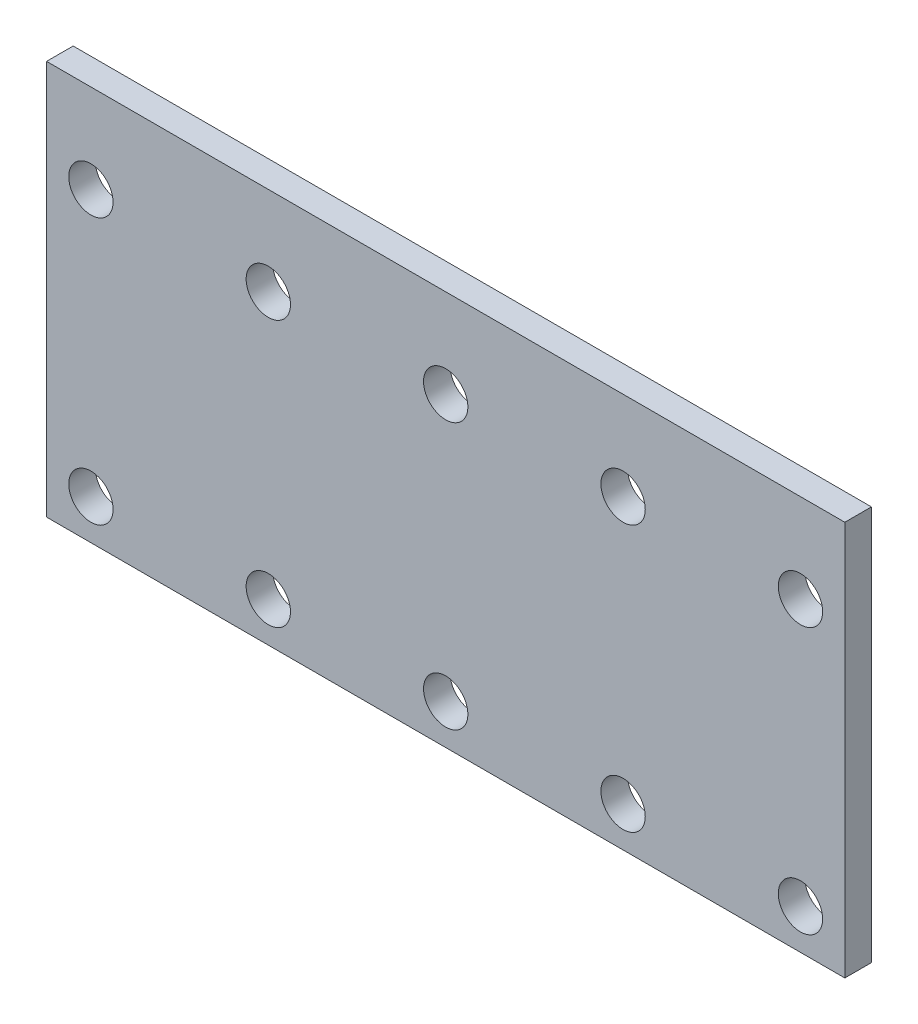
SolidWorks part; units mm, degrees
material "ABS"
ref_plane "Front Plane" through (0, 0, 0) normal (0, 0, 1) x (1, 0, 0)
ref_plane "Top Plane" through (0, 0, 0) normal (0, 1, 0) x (1, 0, 0)
ref_plane "Right Plane" through (0, 0, 0) normal (1, 0, 0) x (0, 0, -1)
sketch "Sketch1" plane through (0, 0, 0) normal (0, 0, 1) x (1, 0, 0)
  line L0 (0, 14.5) -> (0, 44.5)
  line L1 (0, 0) -> (90, 0)
  line L2 (0, 0) -> (0, 14.5)
  line L3 (0, 14.5) -> (90, 14.5)
  line L4 (90, 0) -> (90, 14.5)
  line L5 (0, 44.5) -> (90, 44.5)
  line L6 (90, 44.5) -> (90, 14.5)
  line L7 (0, 4.5) -> (90, 4.5) construction
  line L8 (0, 34.5) -> (90, 34.5) construction
  line L9 (5, 34.5) -> (5, 4.5) construction
  circle A0 centre (5, 34.5) radius 2.5
  circle A1 centre (5, 4.5) radius 2.5
  circle A2 centre (25, 4.5) radius 2.5
  circle A3 centre (25, 34.5) radius 2.5
  circle A4 centre (45, 4.5) radius 2.5
  circle A5 centre (45, 34.5) radius 2.5
  circle A6 centre (65, 4.5) radius 2.5
  circle A7 centre (65, 34.5) radius 2.5
  circle A8 centre (85, 4.5) radius 2.5
  circle A9 centre (85, 34.5) radius 2.5
  point P4 (5, 37)
  point P16 (5, 2)
  dimension "D4" = 5
  dimension "D5" = 5
  dimension "D1" = 10
  dimension "D2" = 20
  dimension "D3" = 90
  dimension "D6" = 5
  dimension "D8" = 2
  dimension "D9" = 10
  dimension "D7" = 5
extrude "Boss-Extrude1" add sketch "Sketch1" along normal blind 3 contours L1 L4 L3 L2 A4 A2 A1 | L6 L5 L0 L3 A5 A3 A0 region at (45, 7.4737, 0) region at (45, 29.3113, 0)
sketch "Sketch2" [suppressed] plane through (0, 0, 0) normal (0, 0, 1) x (1, 0, 0)
  line L0 (0, 20) -> (20, 20) construction
  line L1 (0, 0) -> (40, 0)
  line L2 (0, 0) -> (0, 30)
  line L3 (0, 30) -> (40, 30)
  line L4 (40, 0) -> (40, 30)
  line L5 (20, 20) -> (40, 20) construction
  circle A0 centre (10, 20) radius 2.5
  circle A1 centre (30, 20) radius 2.5
  circle A2 centre (20, 20) radius 2.5
  point P7 (10, 20)
  point P9 (30, 20)
  dimension "D1" = 5
  dimension "D2" = 30
  dimension "D3" = 20
  dimension "D4" = 40
extrude "Boss-Extrude2" [suppressed] add sketch "Sketch2" along normal blind 3
sketch "Sketch3" [suppressed] plane through (0, 0, 0) normal (0, 1, 0) x (1, 0, 0)
  line L0 (0, -10) -> (20, -10) construction
  line L1 (0, 0) -> (40, 0)
  line L2 (0, 0) -> (0, -15)
  line L3 (0, -15) -> (40, -15)
  line L4 (40, 0) -> (40, -15)
  line L5 (20, -10) -> (40, -10) construction
  circle A0 centre (10, -10) radius 2.5
  circle A1 centre (30, -10) radius 2.5
  point P14 (10, -12.5)
  dimension "D3" = 5
  dimension "D1" = 2.5
  dimension "D2" = 10
extrude "Boss-Extrude3" [suppressed] add sketch "Sketch3" along normal blind 3
sketch "Sketch6" [suppressed] plane through (0, 0, 3) normal (0, 0, 1) x (1, 0, 0)
  line L0 (7.5, 20) -> (5.75, 20) construction
  line L1 (5.75, 15.75) -> (5.75, 24.25)
  line L2 (5.75, 24.25) -> (14.25, 24.25)
  line L3 (10, 24.25) -> (10, 22.5) construction
  line L4 (14.25, 15.75) -> (14.25, 24.25)
  line L5 (5.75, 15.75) -> (14.25, 15.75)
  line L6 (20, 30) -> (20, 3) construction
  line L7 (40, 30) -> (0, 30) construction
  line L8 (0, 3) -> (40, 3) construction
  line L9 (34.25, 15.75) -> (25.75, 15.75)
  line L10 (34.25, 15.75) -> (34.25, 24.25)
  line L11 (34.25, 24.25) -> (25.75, 24.25)
  line L12 (25.75, 15.75) -> (25.75, 24.25)
  line L13 (17.5, 20) -> (15.75, 20) construction
  line L14 (15.75, 15.75) -> (15.75, 24.25)
  line L15 (15.75, 24.25) -> (24.25, 24.25)
  line L16 (20, 24.25) -> (20, 22.5) construction
  line L17 (24.25, 15.75) -> (24.25, 24.25)
  line L18 (15.75, 15.75) -> (24.25, 15.75)
  circle A0 centre (10, 20) radius 2.5 construction
  circle A1 centre (20, 20) radius 2.5 construction
  point P11 (14.25, 20)
  point P34 (24.25, 20)
  dimension "D1" = 2
sketch "Sketch4" [suppressed] plane through (0, 3, 0) normal (0, 1, 0) x (1, 0, 0)
  line L1 (5.7783, -15) -> (5.7783, -5.75)
  line L2 (0, -15) -> (40, -15) construction
  line L3 (5.7783, -5.75) -> (14.2217, -5.75)
  line L4 (10, -5.75) -> (10, -7.5) construction
  line L5 (7.5283, -10.375) -> (5.7783, -10.375) construction
  line L6 (14.2217, -15) -> (14.2217, -5.75)
  line L7 (5.7783, -15) -> (14.2217, -15)
  line L8 (20, -15) -> (20, -3) construction
  line L9 (0, -3) -> (40, -3) construction
  line L10 (32.4717, -10.375) -> (34.2217, -10.375) construction
  line L11 (30, -5.75) -> (30, -7.5) construction
  line L12 (34.2217, -15) -> (25.7783, -15)
  line L13 (25.7783, -15) -> (25.7783, -5.75)
  line L14 (34.2217, -5.75) -> (25.7783, -5.75)
  line L15 (34.2217, -15) -> (34.2217, -5.75)
  circle A2 centre (10, -10) radius 2.5 construction
  dimension "D1" = 2
fillet "Fillet2" [suppressed] radius 35
extrude "Cut-Extrude2" [suppressed] cut sketch "Sketch4" along normal through all
extrude "Cut-Extrude4" [suppressed] cut sketch "Sketch6" along normal through all
fillet "Fillet4" [suppressed] radius 1
